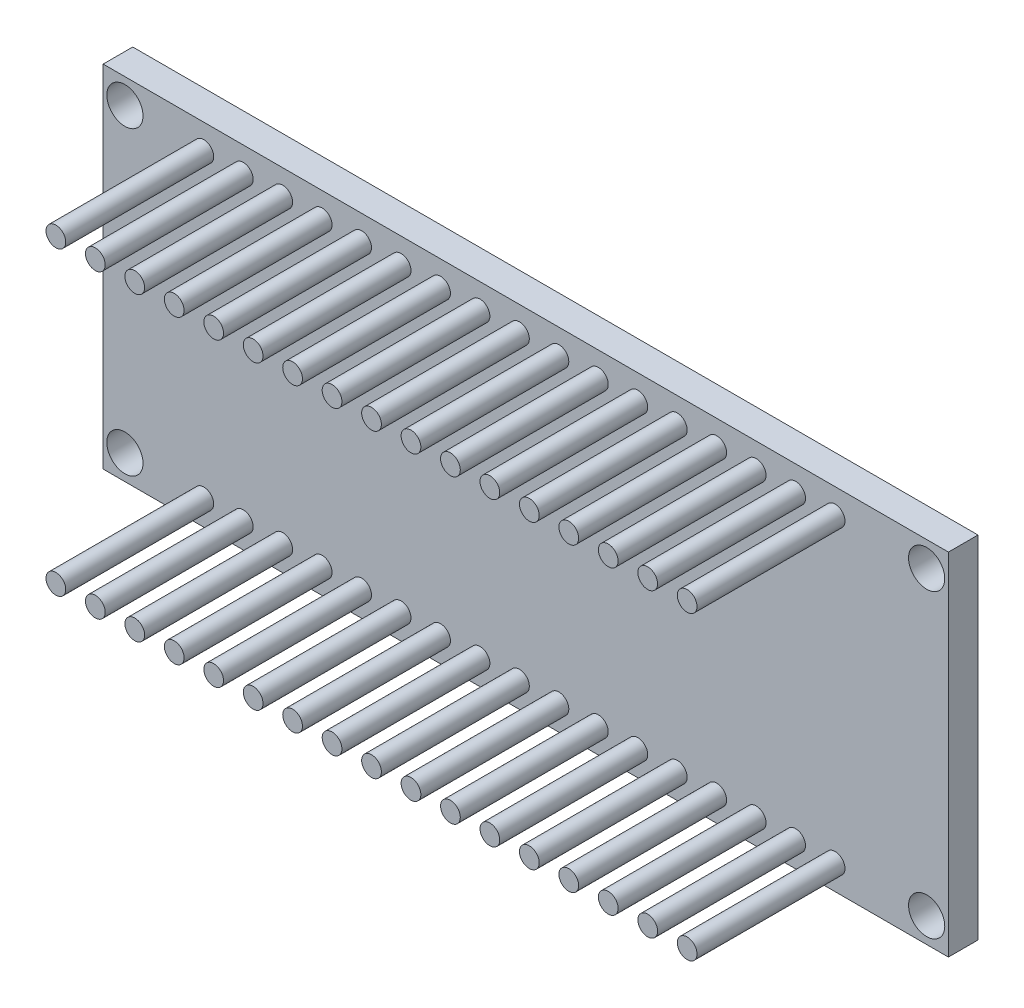
SolidWorks part; units mm, degrees
ref_plane "Front Plane" through (0, 0, 0) normal (0, 0, 1) x (1, 0, 0)
ref_plane "Top Plane" through (0, 0, 0) normal (0, 1, 0) x (1, 0, 0)
ref_plane "Right Plane" through (0, 0, 0) normal (1, 0, 0) x (0, 0, -1)
sketch "Sketch1" plane through (0, 0, 0) normal (0, 0, 1) x (1, 0, 0)
  line L0 (-219.0854, 61.6535) -> (-176.2406, 61.6535) construction
  line L1 (-176.2406, 70.5435) -> (-219.0854, 70.5435)
  line L2 (-176.2406, 70.5435) -> (-176.2406, 52.7635)
  line L3 (-176.2406, 52.7635) -> (-219.0854, 52.7635)
  line L4 (-219.0854, 70.5435) -> (-219.0854, 52.7635)
  line L5 (-197.663, 70.5435) -> (-197.663, 52.7635) construction
  circle A0 centre (-217.983, 69.2785) radius 0.9174
  circle A1 centre (-217.983, 54.0285) radius 0.9174
  circle A2 centre (-177.343, 54.0285) radius 0.9174
  circle A3 centre (-177.343, 69.2785) radius 0.9174
extrude "Boss-Extrude1" add sketch "Sketch1" along normal blind 1.5
sketch "Sketch2" plane through (0, 0, 1.5) normal (0, 0, 1) x (1, 0, 0)
  line L0 (-217.983, 69.2785) -> (-177.343, 69.2785) construction
  line L1 (-219.0854, 61.6535) -> (-203.7997, 61.6535) construction
  line L2 (-219.0854, 70.5435) -> (-219.0854, 52.7635) construction
  circle A0 centre (-213.983, 69.2785) radius 0.5
  circle A2 centre (-213.983, 54.0285) radius 0.5
  circle A3 centre (-211.983, 69.2785) radius 0.5
  circle A4 centre (-211.983, 54.0285) radius 0.5
  circle A5 centre (-209.983, 69.2785) radius 0.5
  circle A6 centre (-209.983, 54.0285) radius 0.5
  circle A7 centre (-207.983, 69.2785) radius 0.5
  circle A8 centre (-207.983, 54.0285) radius 0.5
  circle A9 centre (-205.983, 69.2785) radius 0.5
  circle A10 centre (-205.983, 54.0285) radius 0.5
  circle A11 centre (-203.983, 69.2785) radius 0.5
  circle A12 centre (-203.983, 54.0285) radius 0.5
  circle A13 centre (-201.983, 69.2785) radius 0.5
  circle A14 centre (-201.983, 54.0285) radius 0.5
  circle A15 centre (-199.983, 69.2785) radius 0.5
  circle A16 centre (-199.983, 54.0285) radius 0.5
  circle A17 centre (-197.983, 69.2785) radius 0.5
  circle A18 centre (-197.983, 54.0285) radius 0.5
  circle A19 centre (-195.983, 69.2785) radius 0.5
  circle A20 centre (-195.983, 54.0285) radius 0.5
  circle A21 centre (-193.983, 69.2785) radius 0.5
  circle A22 centre (-193.983, 54.0285) radius 0.5
  circle A23 centre (-191.983, 69.2785) radius 0.5
  circle A24 centre (-191.983, 54.0285) radius 0.5
  circle A25 centre (-189.983, 69.2785) radius 0.5
  circle A26 centre (-189.983, 54.0285) radius 0.5
  circle A27 centre (-187.983, 69.2785) radius 0.5
  circle A28 centre (-187.983, 54.0285) radius 0.5
  circle A29 centre (-185.983, 69.2785) radius 0.5
  circle A30 centre (-185.983, 54.0285) radius 0.5
  circle A31 centre (-183.983, 69.2785) radius 0.5
  circle A32 centre (-183.983, 54.0285) radius 0.5
  circle A33 centre (-181.983, 69.2785) radius 0.5
  circle A34 centre (-181.983, 54.0285) radius 0.5
  dimension "D1" = 17
extrude "Boss-Extrude2" add sketch "Sketch2" along normal blind 7.5
sketch "Sketch3" plane through (0, 0, 0) normal (0, 0, -1) x (-1, 0, 0)
  line L0 (219.0854, 61.6535) -> (176.2406, 61.6535) construction
  line L1 (219.0854, 70.5435) -> (219.0854, 52.7635) construction
  line L2 (176.2406, 52.7635) -> (176.2406, 70.5435) construction
  line L3 (215.3354, 65.1535) -> (220.3354, 65.1535)
  line L4 (215.3354, 65.1535) -> (215.3354, 58.1535)
  line L5 (215.3354, 58.1535) -> (220.3354, 58.1535)
  line L6 (220.3354, 65.1535) -> (220.3354, 58.1535)
  point P8 (176.2406, 61.6535)
extrude "Boss-Extrude3" add sketch "Sketch3" along normal blind 2
fillet "Fillet1" radius 0.75 4 edges at (-219.7104, 65.1535, 0) (-217.8354, 65.1535, -2) (-219.7104, 58.1535, 0) (-217.8354, 58.1535, -2)
